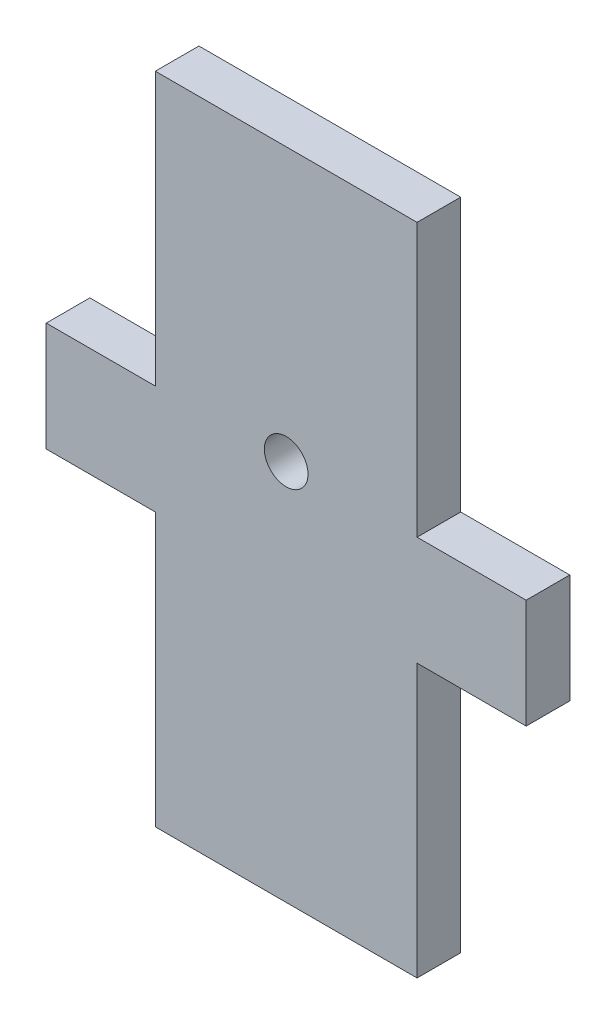
SolidWorks part; units mm, degrees
ref_plane "Front Plane" through (0, 0, 0) normal (0, 0, 1) x (1, 0, 0)
ref_plane "Top Plane" through (0, 0, 0) normal (0, 1, 0) x (1, 0, 0)
ref_plane "Right Plane" through (0, 0, 0) normal (1, 0, 0) x (0, 0, -1)
sketch "Sketch1" plane through (0, 0, 0) normal (0, 0, 1) x (1, 0, 0)
  line L1 (-30, 75) -> (30, 75)
  line L2 (-30, 75) -> (-30, -75)
  line L3 (-30, -75) -> (30, -75)
  line L4 (30, 75) -> (30, -75)
  line L5 (-30, 75) -> (30, -75) construction
  line L6 (-30, -75) -> (30, 75) construction
  point P0 (0, 0)
  dimension "D1" = 30
  dimension "D2" = 75
extrude "Boss-Extrude1" add sketch "Sketch1" against normal blind 10
sketch "Sketch2" plane through (0, 0, 0) normal (0, 0, 1) x (1, 0, 0)
  line L0 (-30, 12.5) -> (-30, -12.5)
  line L2 (30, -75) -> (30, 75) construction
  line L3 (30, 12.5) -> (30, -12.5)
  line L4 (55, 0) -> (55, 12.5)
  line L5 (55, 0) -> (55, -12.5)
  line L6 (55, -12.5) -> (30, -12.5)
  line L7 (55, 12.5) -> (30, 12.5)
  line L11 (-55, 12.5) -> (-30, 12.5)
  line L12 (-55, -12.5) -> (-30, -12.5)
  line L13 (-55, 0) -> (-55, -12.5)
  line L14 (-55, 0) -> (-55, 12.5)
extrude "Boss-Extrude2" add sketch "Sketch2" against normal blind 10
sketch "Sketch3" plane through (0, 0, 0) normal (0, 0, 1) x (1, 0, 0)
  circle A0 centre (0, 12.5) radius 5
extrude "Cut-Extrude1" cut sketch "Sketch3" against normal blind 10
